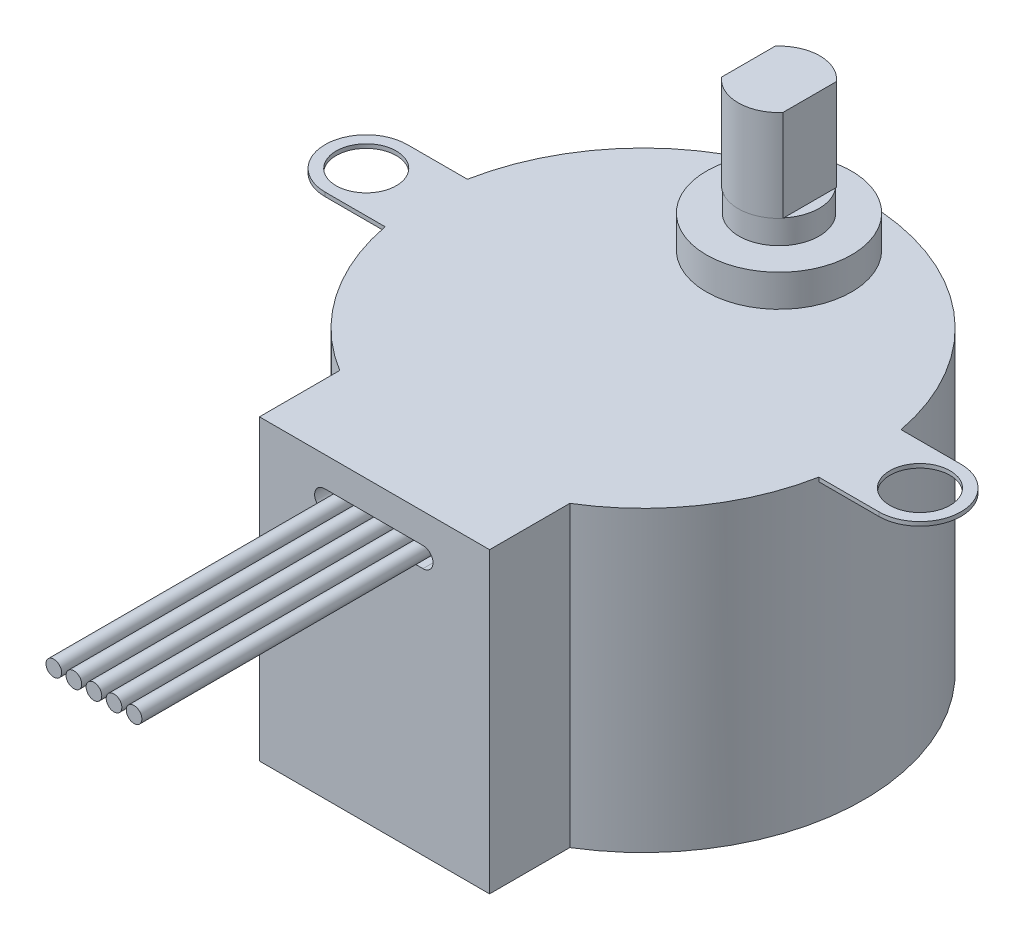
SolidWorks part; units mm, degrees
ref_plane "Front Plane" through (0, 0, 0) normal (0, 0, 1) x (1, 0, 0)
ref_plane "Top Plane" through (0, 0, 0) normal (0, 1, 0) x (1, 0, 0)
ref_plane "Right Plane" through (0, 0, 0) normal (1, 0, 0) x (0, 0, -1)
sketch "Sketch1" plane through (0, 0, 0) normal (0, 1, 0) x (1, 0, 0)
  line L2 (-7.2834, -11.9211) -> (-7.2834, -17.0011)
  line L3 (-7.2834, -17.0011) -> (7.2835, -17.0011)
  line L4 (7.2835, -11.9211) -> (7.2835, -17.0011)
  arc A0 (7.2835, -11.9211) -> (-7.2834, -11.9211) centre (0, 0) ccw
  dimension "D1" = 27.94
  dimension "D2" = 14.5669
  dimension "D3" = 7.2835
  dimension "D4" = 5.08
extrude "Boss-Extrude1" add sketch "Sketch1" along normal blind 18.8722
sketch "Sketch3" plane through (0, 18.8722, 0) normal (0, 1, 0) x (1, 0, 0)
  line L0 (7.2835, -17.0011) -> (7.2835, -11.9211) construction
  circle A1 centre (0.0191, 8.5852) radius 4.5974
  arc A2 (7.2835, -11.9211) -> (-7.2834, -11.9211) centre (0, 0) ccw construction
  circle A3 centre (0.0191, 8.5852) radius 2.54
  point P5 (0, 13.97)
  dimension "D1" = 9.1948
  dimension "D2" = 5.3848
  dimension "D4" = 5.08
  dimension "D3" = 7.2644
extrude "Boss-Extrude2" add sketch "Sketch3" along normal blind 2.032
extrude "Boss-Extrude3" add sketch "Sketch3<2>" along normal blind 2.032
sketch "Sketch3<2>" plane through (0, 18.8722, 0) normal (0, 1, 0) x (1, 0, 0) same geometry as "Sketch3"
sketch "Sketch4" plane through (0, 18.8722, 0) normal (0, 1, 0) x (1, 0, 0)
  circle A0 centre (0.0191, 8.5852) radius 2.54
extrude "Boss-Extrude4" add sketch "Sketch4" along normal blind 3.556
sketch "Sketch5" plane through (0, 22.4282, 0) normal (0, 1, 0) x (1, 0, 0)
  line L0 (-1.9215, 10.287) -> (-1.9215, 6.8834)
  line L1 (1.9596, 10.287) -> (1.9596, 6.8834)
  arc A0 (-1.9215, 6.8834) -> (1.9596, 6.8834) centre (0.0191, 8.5852) ccw
  arc A1 (1.9596, 10.287) -> (-1.9215, 10.287) centre (0.0191, 8.5852) ccw
  dimension "D3" = 2.581
  dimension "D1" = 3.4036
  dimension "D2" = 3.4036
extrude "Boss-Extrude5" add sketch "Sketch5" along normal blind 5.8039
sketch "Sketch6" plane through (0, 0, 17.0011) normal (0, 0, 1) x (1, 0, 0)
  line L0 (-3.1559, 16.3593) -> (3.0671, 16.3593) construction
  line L1 (-3.1559, 16.9943) -> (3.0671, 16.9943)
  line L2 (-3.1559, 15.7243) -> (3.0671, 15.7243)
  line L3 (-7.2834, 18.8722) -> (-7.2834, 0) construction
  arc A0 (-3.1559, 16.9943) -> (-3.1559, 15.7243) centre (-3.1559, 16.3593) ccw
  arc A1 (3.0671, 15.7243) -> (3.0671, 16.9943) centre (3.0671, 16.3593) ccw
  point P2 (-0.0444, 16.3593)
  dimension "D1" = 6.223
  dimension "D2" = 7.239
  dimension "D3" = 1.27
extrude "Cut-Extrude1" cut sketch "Sketch6" against normal blind 7.62
sketch "Sketch7" plane through (0, 0, 9.3811) normal (0, 0, 1) x (1, 0, 0)
  circle A0 centre (-2.5209, 16.3631) radius 0.4953
  circle A1 centre (-1.2509, 16.3631) radius 0.4953
  circle A2 centre (0.0191, 16.3631) radius 0.4953
  circle A3 centre (1.2891, 16.3631) radius 0.4953
  circle A4 centre (2.5591, 16.3631) radius 0.4953
  arc A5 (-3.1559, 16.9943) -> (-3.1559, 15.7243) centre (-3.1559, 16.3593) ccw construction
  point P13 (-3.7909, 16.3593)
  dimension "D1" = 0.9906
  dimension "D2" = 0.9906
  dimension "D3" = 0.9906
  dimension "D4" = 0.9906
  dimension "D5" = 0.9906
  dimension "D6" = 1.27
  dimension "D7" = 1.27
  dimension "D8" = 1.27
  dimension "D9" = 1.27
  dimension "D10" = 1.27
extrude "Boss-Extrude6" add sketch "Sketch7" along normal blind 25.4
sketch "Sketch8" plane through (0, 18.8722, 0) normal (0, 1, 0) x (1, 0, 0)
  line L0 (-17.526, 0) -> (17.526, 0) construction
  line L1 (-17.526, 2.6032) -> (17.526, 2.6032)
  line L2 (-17.526, -2.6032) -> (17.526, -2.6032)
  arc A0 (-17.526, 2.6032) -> (-17.526, -2.6032) centre (-17.526, 0) ccw
  arc A1 (17.526, -2.6032) -> (17.526, 2.6032) centre (17.526, 0) ccw
  circle A3 centre (-17.526, 0) radius 1.905
  circle A4 centre (17.526, 0) radius 1.905
  point P3 (0, 0)
  dimension "D2" = 0
  dimension "D3" = 3.81
  dimension "D4" = 3.81
  dimension "D1" = 35.052
extrude "Boss-Extrude7" add sketch "Sketch8" against normal blind 0.254
